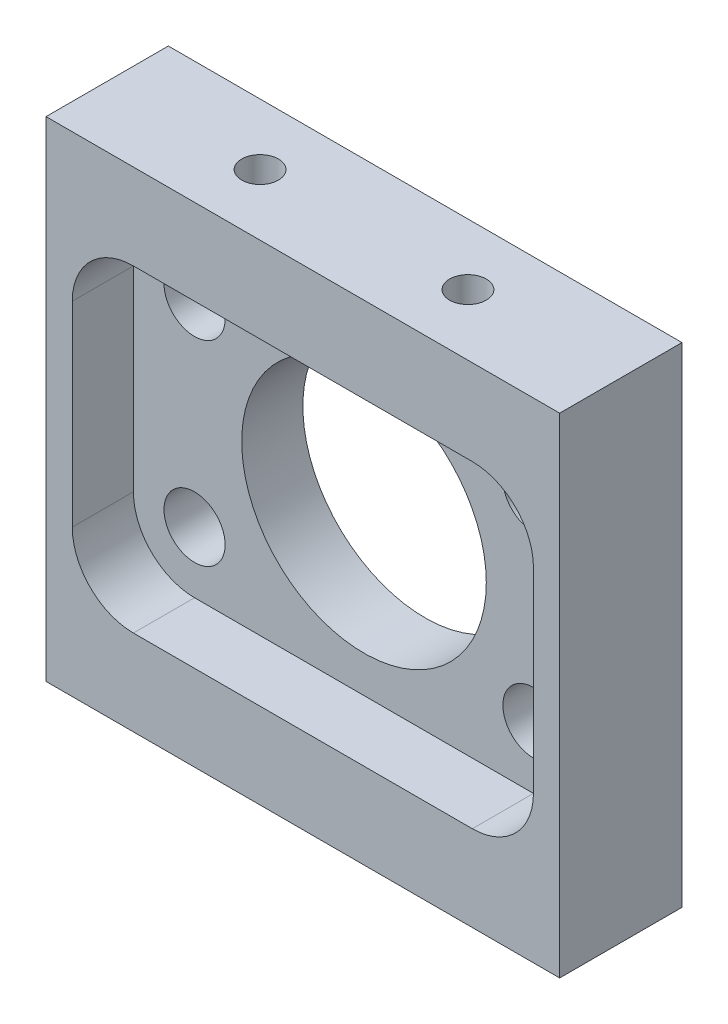
SolidWorks part; units mm, degrees
material "PVC hart"
ref_plane "Ebene vorne" through (0, 0, 0) normal (0, 0, 1) x (1, 0, 0)
ref_plane "Ebene oben" through (0, 0, 0) normal (0, 1, 0) x (1, 0, 0)
ref_plane "Ebene rechts" through (0, 0, 0) normal (1, 0, 0) x (0, 0, -1)
sketch "Skizze1" plane through (0, 0, 0) normal (0, 0, 1) x (1, 0, 0)
  line L0 (-10.5, 0) -> (10.5, 0) construction
  line L1 (-10.5, 10) -> (10.5, 10)
  line L2 (-10.5, 10) -> (-10.5, -10)
  line L3 (-10.5, -10) -> (10.5, -10)
  line L4 (10.5, 10) -> (10.5, -10)
  line L5 (6.9282, 4) -> (-6.9282, -4) construction
  line L6 (-6.9282, 4) -> (6.9282, -4) construction
  line L7 (-6.9282, 6.5) -> (6.9282, 6.5)
  line L8 (0, 6.5) -> (0, -6.5) construction
  line L9 (-9.4282, 4) -> (-9.4282, -4)
  line L10 (9.4282, 4) -> (9.4282, -4)
  line L11 (-6.9282, -6.5) -> (6.9282, -6.5)
  circle A0 centre (0, 0) radius 5
  circle A1 centre (6.9282, 4) radius 1.25
  circle A2 centre (-6.9282, -4) radius 1.25
  circle A3 centre (0, 0) radius 8 construction
  circle A4 centre (-6.9282, 4) radius 1.25
  circle A5 centre (6.9282, -4) radius 1.25
  arc A6 (-6.9282, 6.5) -> (-9.4282, 4) centre (-6.9282, 4) ccw
  arc A8 (6.9282, 6.5) -> (9.4282, 4) centre (6.9282, 4) cw
  arc A9 (6.9282, -6.5) -> (9.4282, -4) centre (6.9282, -4) ccw
  arc A11 (-6.9282, -6.5) -> (-9.4282, -4) centre (-6.9282, -4) cw
  point P27 (-9.4282, 0)
  point P34 (9.4282, 0)
  dimension "D1" = 2.5
  dimension "D2" = 16
  dimension "D4" = 10
  dimension "D8" = 2.5
  dimension "D3" = 60
  dimension "D5" = 20
  dimension "D6" = 21
  dimension "D9" = 1.0718
extrude "Aufsatz-Linear austragen1" add sketch "Skizze1" along normal mid plane 5 contours L4 L1 L2 L3 A0 | A1 | A2 region at (0, 9.71, 0) region at (0, 6.271, 0)
extrude "Schnitt-Linear austragen1" cut sketch "Skizze1<3>" against normal blind 2.5 from surface contours A8 L10 A9 L11 A11 L9 A6 L7 starting at face at (0, 0, 2.5)
sketch "Skizze1<3>" plane through (0, 0, 0) normal (0, 0, 1) x (1, 0, 0) same geometry as "Skizze1"
sketch "Skizze4" plane through (0, 10, 0) normal (0, 1, 0) x (1, 0, 0)
  line L0 (-4.25, 0) -> (4.25, 0) construction
  circle A0 centre (-4.25, 0) radius 0.75
  circle A1 centre (4.25, 0) radius 0.75
  dimension "D1" = 1.5
  dimension "D2" = 8.5
extrude "Schnitt-Linear austragen2" cut sketch "Skizze4" against normal blind 3
mirror "Spiegeln1" about plane through (0, 0, 0) normal (0, 1, 0) of "Schnitt-Linear austragen2"
